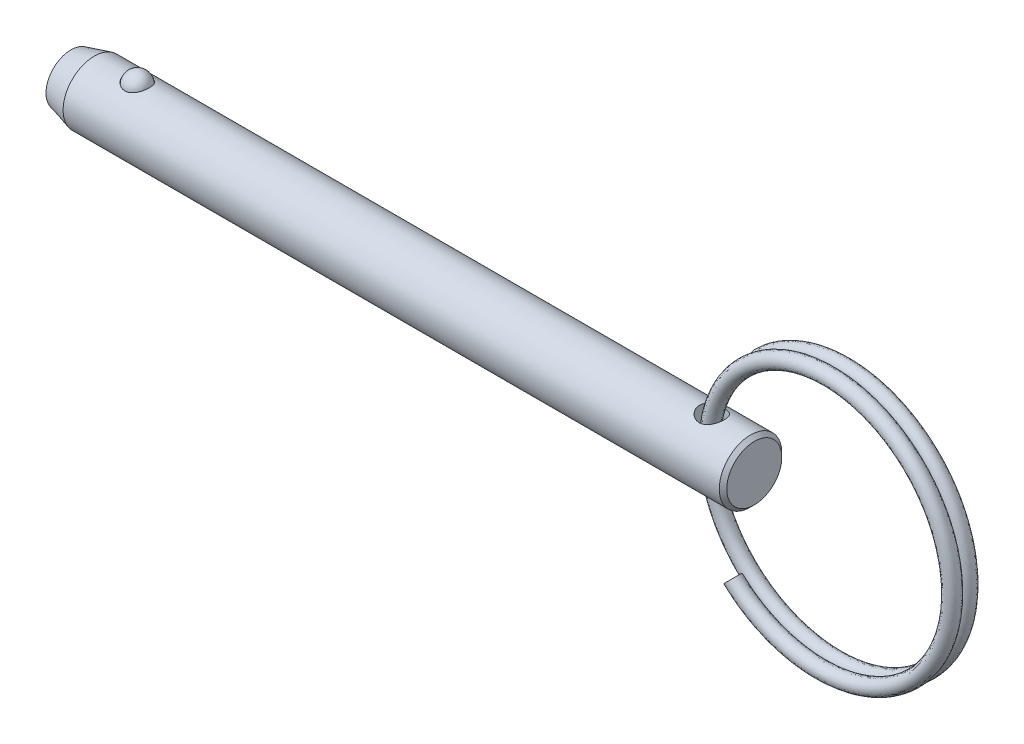
SolidWorks part; units mm, degrees
ref_plane "Front" through (0, 0, 0) normal (0, 0, 1) x (1, 0, 0)
ref_plane "Top" through (0, 0, 0) normal (0, 1, 0) x (1, 0, 0)
ref_plane "Right" through (0, 0, 0) normal (1, 0, 0) x (0, 0, -1)
sketch "Sketch1" plane through (0, 0, 0) normal (0, 0, 1) x (1, 0, 0)
  line L0 (34.6964, 2.794) -> (34.3154, 3.175)
  line L1 (34.3154, 3.175) -> (34.6964, 3.175) construction
  line L4 (34.6964, 2.794) -> (34.6964, 0)
  line L5 (34.6964, 3.175) -> (34.6964, 2.794) construction
  line L16 (34.3154, 3.175) -> (-32.3265, 3.175)
  line L17 (-34.6964, 3.175) -> (-34.6964, 2.54) construction
  line L19 (-32.3265, 3.175) -> (-34.6964, 3.175) construction
  line L22 (-34.6964, -3.175) -> (-32.3265, -3.175) construction
  line L23 (-27.9619, 2.8575) -> (-27.9619, -2.8575) construction
  line L24 (-34.6964, 0) -> (34.6964, 0)
  line L27 (34.6964, 0) -> (37.4904, 0) construction
  line L29 (-34.6964, 0) -> (-34.6964, -2.54) construction
  line L36 (29.1084, 0) -> (29.1084, 3.175) construction
  line L37 (-34.6964, 2.54) -> (-34.6964, 0)
  line L38 (-32.3265, -3.175) -> (34.6964, -3.175) construction
  line L39 (-34.6964, -2.54) -> (-34.6964, -3.175) construction
  line L40 (-32.3265, 3.175) -> (-34.6964, 2.54)
  line L42 (-32.3265, -3.175) -> (-34.6964, -2.54) construction
  line L43 (-32.3265, 3.175) -> (-32.3265, -3.175) construction
  circle A2 centre (-27.9619, 2.8575) radius 1.2319 construction
  point P35 (-26.7716, 3.175)
  dimension "A1" = 15
revolve "Revolve1" add sketch "Sketch1" angle 360 about L27
sketch "Sketch2" plane through (0, 0, 0) normal (0, 0, 1) x (1, 0, 0)
  line L0 (-26.7046, 2.8575) -> (-29.2192, 2.8575)
  line L1 (-27.9619, 4.0894) -> (-27.9619, 4.1148) construction
  line L2 (-26.7046, 2.8575) -> (-24.19, 2.8575) construction
  circle A0 centre (-27.9619, 2.8575) radius 1.2319 construction
  circle A1 centre (-27.9619, 2.8575) radius 1.2319 construction
  arc A2 (-29.2192, 2.8575) -> (-26.7046, 2.8575) centre (-27.9619, 2.8575) cw
  dimension "D1" = 0.0254
revolve "Cut-Revolve1" cut sketch "Sketch2" angle 360 about L2
sketch "Sketch3" plane through (0, 0, 0) normal (0, 0, 1) x (1, 0, 0)
  line L0 (-26.73, 2.8575) -> (-29.1938, 2.8575)
  line L1 (-26.73, 2.8575) -> (-24.2662, 2.8575) construction
  circle A0 centre (-27.9619, 2.8575) radius 1.2319 construction
  arc A1 (-26.73, 2.8575) -> (-29.1938, 2.8575) centre (-27.9619, 2.8575) ccw
revolve "Revolve2" add sketch "Sketch3" angle 360 about L1
sketch "Sketch4" plane through (0, 0, 0) normal (0, 0, 1) x (1, 0, 0)
  line L1 (30.3784, -3.175) -> (31.6484, -3.175)
  line L2 (30.3784, -3.175) -> (30.3784, 3.175)
  line L3 (30.3784, 3.175) -> (31.6484, 3.175)
  line L4 (31.6484, -3.175) -> (31.6484, 3.175)
  line L5 (30.3784, -3.175) -> (30.3784, -4.445) construction
  line L6 (31.6484, 3.175) -> (34.6964, 3.175) construction
  line L8 (29.1084, -3.175) -> (29.1084, 3.175) construction
  line L9 (29.1084, 0) -> (30.3784, 0) construction
  line L11 (30.3784, 0) -> (31.6484, 0) construction
  line L12 (34.3154, 3.175) -> (-32.3265, 3.175) construction
  line L14 (-32.3265, -3.175) -> (34.6964, -3.175) construction
  dimension "D1" = 2.54
revolve "Cut-Revolve2" cut sketch "Sketch4" angle 360 about L2
sketch "Sketch5" plane through (0, 0, 0) normal (0, 0, 1) x (1, 0, 0)
  line L0 (0, 0) -> (29.4014, 0) construction
  line L1 (29.4014, 0) -> (29.4014, 3.175) construction
  line L2 (34.3154, 3.175) -> (-32.3265, 3.175) construction
  line L3 (42.8634, 0) -> (56.3254, 0) construction
  line L4 (31.6484, 3.175) -> (31.3554, 3.175) construction
  line L5 (30.3784, 3.175) -> (31.6484, 3.175) construction
  line L6 (29.7812, 3.175) -> (29.7812, -3.175) construction
  line L7 (29.4014, 3.175) -> (29.1084, 3.175) construction
  line L8 (30.3784, -3.175) -> (31.6484, -3.175) construction
  line L9 (29.7812, -3.175) -> (31.6484, -3.175) construction
  line L10 (29.4014, 0) -> (42.8634, 0) construction
  line L12 (31.3554, 3.175) -> (29.7812, 3.175) construction
  line L13 (42.8634, 11.938) -> (42.8634, 13.462) construction
  circle A0 centre (42.8634, 0) radius 13.462
  circle A1 centre (42.8634, 0) radius 11.938 construction
  circle A2 centre (42.8634, 0) radius 12.7 construction
  point P26 (42.8634, 12.7)
curve "Helix/Spiral1" pitch 1.5494 height 1.3557 radius 13.462 left hand yes centre (42.8634, 0, 0) axis (0, 0, -1) start towards (1, 0, 0)
sketch "Sketch6" plane through (114.0038, 0, 0) normal (0, 1, 0) x (0, 0, -1)
  line L0 (0, 83.0784) -> (0, 83.8404) construction
  line L1 (0, 83.8404) -> (0, 84.6024) construction
  circle A0 centre (0, 83.8404) radius 0.762
  dimension "D1" = 1.524
sketch "Sketch7" plane through (0, 0, 0) normal (0, 0, 1) x (1, 0, 0)
  circle A0 centre (42.8634, 0) radius 13.462 construction
  circle A1 centre (42.8634, 0) radius 13.462
curve "Helix/Spiral2" pitch 1.5494 height 1.3557 radius 13.462 left hand yes centre (42.8634, 0, 0) axis (0, 0, 1) start towards (1, 0, 0)
sweep "Sweep1" add profiles "Sketch6" path "Helix/Spiral1"
sweep "Sweep2" add profiles "Sketch6<2>" path "Helix/Spiral2"
sketch "Sketch6<2>" plane through (114.0038, 0, 0) normal (0, 1, 0) x (0, 0, -1) same geometry as "Sketch6"
equation "\"D12@Sketch1\"=\"A@Sketch1\" * 0.80"
equation "\"D2@Sketch1\"=\"A@Sketch1\" * 0.9"
equation "\"D1@Sketch4\" = \"A@Sketch1\" / 2.5"
equation "\"Ring OD@Sketch5\" = \"R Ring Dia@Sketch5\" * 0.06"
equation "\"D4@Helix/Spiral1\"=\"Ring OD@Sketch5\" + 0.001"
equation "\"D1@Sketch6\"=\"Ring OD@Sketch5\""
equation "\"D4@Helix/Spiral2\" = \"D4@Helix/Spiral1\""
equation "\"D5@Helix/Spiral2\" = \"D5@Helix/Spiral1\""
